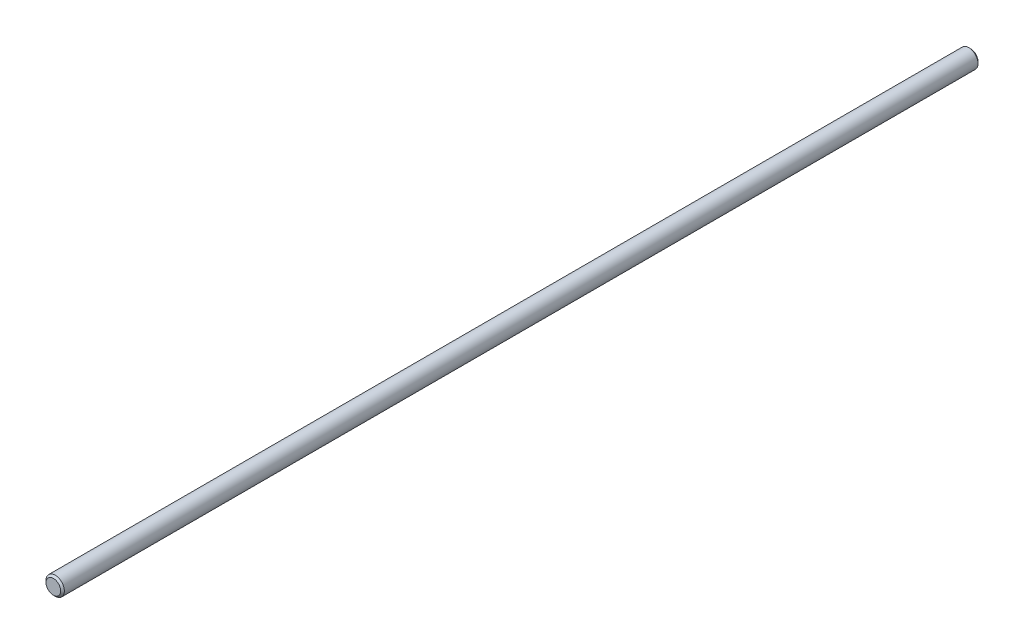
SolidWorks part; units mm, degrees
ref_plane "Front" through (0, 0, 0) normal (0, 0, 1) x (1, 0, 0)
ref_plane "Top" through (0, 0, 0) normal (0, 1, 0) x (1, 0, 0)
ref_plane "Right" through (0, 0, 0) normal (1, 0, 0) x (0, 0, -1)
sketch "Sketch1" plane through (0, 0, 0) normal (0, 0, 1) x (1, 0, 0)
  circle A0 centre (0, 0) radius 4
  dimension "dia" = 8
extrude "Extrude1" add sketch "Sketch1" along normal mid plane 400
sketch "Sketch2" plane through (0, 0, 0) normal (1, 0, 0) x (0, 0, -1)
  point P0 (-200, 4)
  point P1 (200, 4)
chamfer "Chamfer1" distance 0.8 angle 45 2 edges at (4, 0, -200) (4, 0, 200)
equation "\"D1@Chamfer1\" = \"dia@Sketch1\" * .1"
